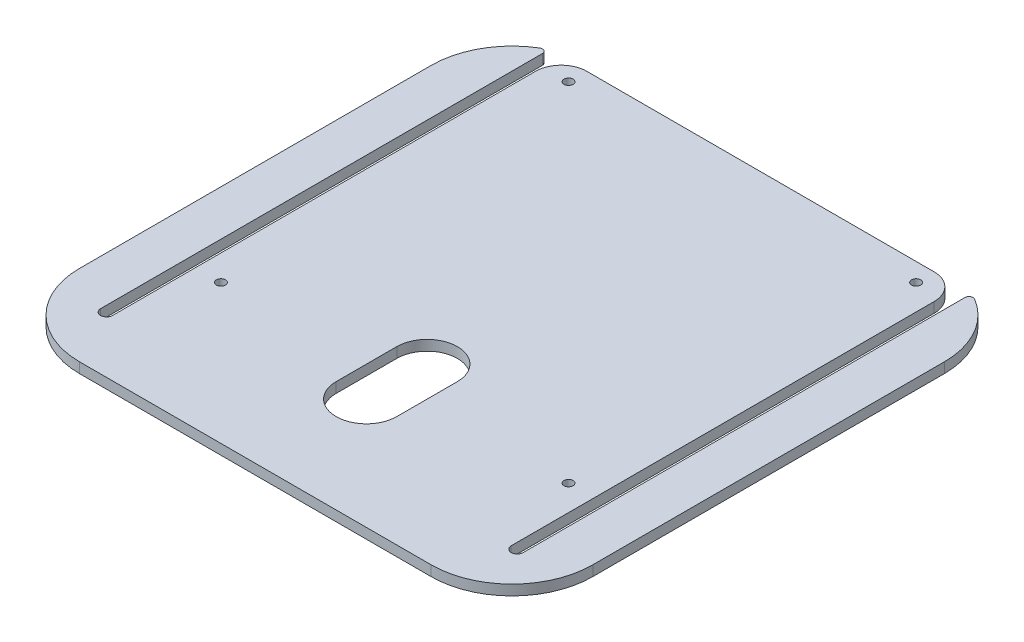
SolidWorks part; units mm, degrees
ref_plane "Front Plane" through (0, 0, 0) normal (0, 0, 1) x (1, 0, 0)
ref_plane "Top Plane" through (0, 0, 0) normal (0, 1, 0) x (1, 0, 0)
ref_plane "Right Plane" through (0, 0, 0) normal (1, 0, 0) x (0, 0, -1)
sketch "Sketch1" plane through (0, 0, 0) normal (0, 1, 0) x (1, 0, 0)
  line L0 (114.3, 0) -> (114.3, -111) construction
  line L1 (0, 0) -> (127, 0)
  line L2 (0, 0) -> (0, -95)
  line L3 (0, -95) -> (127, -95)
  line L4 (127, 0) -> (127, -95)
  line L5 (115.775, 0) -> (115.775, -111)
  line L6 (112.825, 0) -> (112.825, -111)
  line L7 (12.7, 0) -> (12.7, -111) construction
  line L8 (63.5, 0) -> (63.5, -95) construction
  line L9 (14.175, 0) -> (14.175, -111)
  line L10 (11.225, 0) -> (11.225, -111)
  line L11 (63.5, -82.5) -> (63.5, -97.5) construction
  line L12 (0, -95) -> (127, -95)
  line L13 (0, -95) -> (0, -125)
  line L14 (0, -125) -> (127, -125)
  line L15 (127, -95) -> (127, -125)
  line L17 (38.5, -22.5) -> (88.5, -22.5) construction
  line L18 (38.5, -22.5) -> (38.5, -72.5) construction
  line L19 (38.5, -72.5) -> (88.5, -72.5) construction
  line L20 (88.5, -22.5) -> (88.5, -72.5) construction
  line L21 (38.5, -22.5) -> (88.5, -72.5) construction
  line L22 (38.5, -72.5) -> (88.5, -22.5) construction
  line L28 (20.5, -4.5) -> (106.5, -4.5) construction
  line L29 (20.5, -4.5) -> (20.5, -90.5) construction
  line L30 (20.5, -90.5) -> (106.5, -90.5) construction
  line L31 (106.5, -4.5) -> (106.5, -90.5) construction
  line L32 (63.5, -90.5) -> (63.5, -4.5) construction
  line L33 (20.5, -47.5) -> (106.5, -47.5) construction
  line L34 (71, -82.5) -> (71, -97.5)
  line L35 (56, -82.5) -> (56, -97.5)
  line L38 (12.7, -47.5) -> (63.5, -47.5) construction
  line L39 (63.5, -47.5) -> (114.3, -47.5) construction
  line L40 (0, -47.5) -> (127, -47.5) construction
  circle A32 centre (12.7, -47.5) radius 1.4732
  circle A33 centre (114.3, -47.5) radius 1.4732
  arc A35 (115.775, 0) -> (112.825, 0) centre (114.3, 0) ccw
  arc A36 (112.825, -111) -> (115.775, -111) centre (114.3, -111) ccw
  arc A37 (14.175, 0) -> (11.225, 0) centre (12.7, 0) ccw
  arc A38 (11.225, -111) -> (14.175, -111) centre (12.7, -111) ccw
  circle A39 centre (63.5, -47.5) radius 2.7901
  circle A40 centre (20.5, -4.5) radius 1.13
  circle A41 centre (106.5, -4.5) radius 1.13
  circle A42 centre (106.5, -90.5) radius 1.13
  circle A43 centre (20.5, -90.5) radius 1.13
  circle A44 centre (63.5, -47.5) radius 38.5 construction
  arc A45 (71, -82.5) -> (56, -82.5) centre (63.5, -82.5) ccw
  arc A46 (56, -97.5) -> (71, -97.5) centre (63.5, -97.5) ccw
  point P5 (114.3, -55.5)
  point P11 (63.5, -22.5)
  point P13 (88.5, -47.5)
  point P18 (63.5, -47.5)
  point P23 (12.7, -55.5)
  point P44 (63.5, -47.5)
  point P47 (63.5, -90)
  dimension "D2" = 2.9464
  dimension "D5" = 1.475
  dimension "D9" = 2.26
  dimension "D12" = 77
  dimension "D4" = 127
  dimension "D7" = 50
  dimension "D3" = 95
  dimension "D15" = 50.8
  dimension "D8" = 30
  dimension "D6" = 63.5
  dimension "D10" = 86
  dimension "D11" = 86
  dimension "D13" = 15
  dimension "D14" = 8
  dimension "D16" = 15
  dimension "D17" = 63.5
  dimension "D18" = 47.5
extrude "Boss-Extrude1" add sketch "Sketch1" along normal blind 2.54 contours A38 L10 L1 L2 L3 L4 L5 A36 L6 L9 | L10 L1 L2 L3 | L1 L9 L3 L6 A39 | L1 L5 L3 L4 | A39 region at (5.6125, 0, 47.5) region at (63.5, 0, 110.555) region at (63.5, 0, 1.3696) region at (121.3875, 0, 47.5) region at (63.5, 0, 47.5)
fillet "Fillet1" radius 20 4 edges at (0, 1.27, 0) (127, 1.27, 0) (127, 1.27, 125) (0, 1.27, 125)
fillet "Fillet6" radius 6.35 2 edges at (14.175, 1.27, 0) (112.825, 1.27, 0)
fillet "Fillet7" radius 1 2 edges at (115.775, 1.27, 0) (11.225, 1.27, 0)
sketch "Sketch2" plane through (0, 2.54, 0) normal (0, 1, 0) x (1, 0, 0)
  circle A0 centre (63.5, -47.5) radius 14.1031 construction
  circle A1 centre (63.5, -47.5) radius 2.7901 construction
hole_wizard "#4-40 Tapped Hole1" positions "3DSketch1" profile "Sketch3" tap size "#4-40" standard "ANSI Inch" end condition through all
sketch3d "3DSketch1"
  line L0 (106.5, 2.54, 4.5) -> (106.5, 0, 4.5) construction
  line L1 (20.5, 2.54, 4.5) -> (20.5, 0, 4.5) construction
  line L2 (106.5, 2.54, 90.5) -> (106.5, 0, 90.5) construction
  line L3 (20.5, 2.54, 90.5) -> (20.5, 0, 90.5) construction
  point P0 (106.5, 2.54, 4.5)
  point P4 (20.5, 2.54, 4.5)
  point P8 (106.5, 2.54, 90.5)
  point P12 (20.5, 2.54, 90.5)
sketch "Sketch3" plane through (106.5, 2.54, 4.5) normal (1, 0, 0) x (0, 0, 1)
  line L0 (0, 0) -> (0, 2.54)
  line L1 (0, 2.54) -> (1.1303, 2.54)
  line L2 (1.1303, 2.54) -> (1.1303, 0)
  line L5 (1.1303, 0) -> (0, 0)
  line L11 (0, -6.35) -> (0, 107.95) construction
  dimension "Thru Tap Drill Dia." = 2.2606
  dimension "Thru Tap Drill Depth" = 2.54
cosmetic thread "Hole Thread1" parameters "D2"=2.8448
cosmetic thread "Hole Thread2" parameters "D2"=2.8448
cosmetic thread "Hole Thread3" parameters "D2"=2.8448
cosmetic thread "Hole Thread4" parameters "D2"=2.8448
equation "\"D6@Sketch1\"=34.45mm+29.05"
